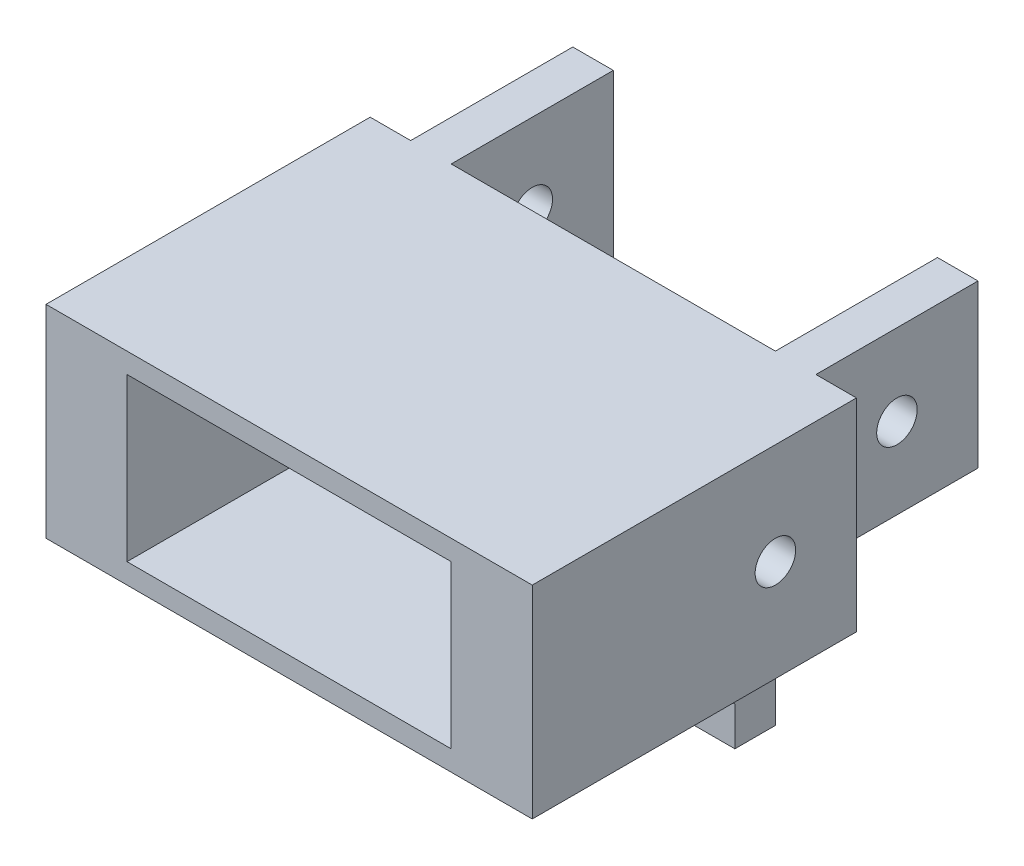
SolidWorks part; units mm, degrees
note: The reader was unsure of these and kept them because the rebuilt part matched: shared geometry of "Esquisse1<6>", "Esquisse1<8>", "Esquisse1<9>", "Esquisse37<5>".
ref_plane "Plan de face" through (0, 0, 0) normal (0, 0, 1) x (1, 0, 0)
ref_plane "Plan de dessus" through (0, 0, 0) normal (0, 1, 0) x (1, 0, 0)
ref_plane "Plan de droite" through (0, 0, 0) normal (1, 0, 0) x (0, 0, -1)
sketch "Esquisse1" plane through (0, 0, 0) normal (0, 0, 1) x (1, 0, 0)
  line L0 (-16.8286, 20.0498) -> (23.1714, 20.0498)
  line L1 (23.1714, 20.0498) -> (23.1714, 0.0498)
  line L2 (23.1714, 0.0498) -> (28.1714, 0.0498)
  line L3 (28.1714, 0.0498) -> (28.1714, 20.0498)
  line L4 (33.1714, 20.0498) -> (33.1714, -4.9502)
  line L5 (33.1714, -4.9502) -> (23.1714, -4.9502)
  line L6 (23.1714, -4.9502) -> (23.1714, -19.9502)
  line L7 (23.1714, -19.9502) -> (-16.8286, -19.9502)
  line L8 (-16.8286, -19.9502) -> (-16.8286, -4.9502)
  line L9 (-16.8286, -4.9502) -> (-26.8286, -4.9502)
  line L10 (-26.8286, -4.9502) -> (-26.8286, 20.0498)
  line L11 (28.1714, 20.0498) -> (33.1714, 20.0498)
  line L12 (-26.8286, 20.0498) -> (-21.8286, 20.0498)
  line L13 (-21.8286, 20.0498) -> (-21.8286, 0.0498)
  line L14 (-21.8286, 0.0498) -> (-16.8286, 0.0498)
  line L15 (-16.8286, 0.0498) -> (-16.8286, 20.0498)
  line L16 (-21.8286, 20.0498) -> (-16.8286, 20.0498)
  line L17 (23.1714, 20.0498) -> (28.1714, 20.0498)
  line L18 (23.1714, -4.9502) -> (-16.8286, -4.9502)
  circle A0 centre (-6.8286, -9.9502) radius 2.5
  circle A1 centre (13.1714, -9.9502) radius 2.5
  dimension "D19" = 5
  dimension "D20" = 5
  dimension "D21" = 10
  dimension "D22" = 5
  dimension "D23" = 5
  dimension "D24" = 10
  dimension "D1" = 20
  dimension "D2" = 40
  dimension "D3" = 5
  dimension "D4" = 20
  dimension "D5" = 5
  dimension "D6" = 25
  dimension "D7" = 10
  dimension "D8" = 15
  dimension "D9" = 40
  dimension "D10" = 15
  dimension "D11" = 10
  dimension "D12" = 25
  dimension "D13" = 5
  dimension "D14" = 20
  dimension "D15" = 5
  dimension "D16" = 20
  dimension "D17" = 5
  dimension "D18" = 5
extrude "Boss.-Extru.2" add sketch "Esquisse1" along normal blind 5 contours L18 L8 L7 L6
sketch "Esquisse10" plane through (0, 0, 5) normal (0, 0, 1) x (1, 0, 0)
  point P0 (13.1714, -9.9502)
hole_wizard "Diamètre du perçage Ø5.0 (5)1" positions "Esquisse10" profile "Esquisse9" hole size "Ø5.0" standard "BSI" end condition through all
sketch "Esquisse9" plane through (13.1714, -9.9502, 5) normal (1, 0, 0) x (0, -1, 0)
  line L0 (0, 0) -> (0, 5)
  line L1 (0, 5) -> (2.5, 5)
  line L2 (2.5, 5) -> (2.5, 0)
  line L5 (2.5, 0) -> (0, 0)
  line L11 (0, -6.35) -> (0, 107.95) construction
  dimension "Diamètre du perçage jusqu'au prochain" = 5
  dimension "Profondeur du perçage jusqu'au prochain" = 5
sketch "Esquisse13" plane through (0, 0, 5) normal (0, 0, 1) x (1, 0, 0)
  point P0 (-6.8286, -9.9502)
hole_wizard "Diamètre du perçage Ø5.0 (5)2" positions "Esquisse13" profile "Esquisse12" hole size "Ø5.0" standard "BSI" end condition through all
sketch "Esquisse12" plane through (-6.8286, -9.9502, 5) normal (1, 0, 0) x (0, -1, 0)
  line L0 (0, 0) -> (0, 5)
  line L1 (0, 5) -> (2.5, 5)
  line L2 (2.5, 5) -> (2.5, 0)
  line L5 (2.5, 0) -> (0, 0)
  line L11 (0, -6.35) -> (0, 107.95) construction
  dimension "Diamètre du perçage jusqu'au prochain" = 5
  dimension "Profondeur du perçage jusqu'au prochain" = 5
extrude "Boss.-Extru.3" add sketch "Esquisse1<6>" along normal blind 40 contours L9 L10 L12 L16 L0 L17 L11 L4 L5 L18
sketch "Esquisse1<6>" plane through (0, 0, 0) normal (0, 0, 1) x (1, 0, 0) same geometry as "Esquisse1"
extrude "Boss.-Extru.4" add sketch "Esquisse1<8>" against normal blind 20 contours L17 L3 L2 L1
sketch "Esquisse1<8>" plane through (0, 0, 0) normal (0, 0, 1) x (1, 0, 0) same geometry as "Esquisse1"
extrude "Boss.-Extru.5" add sketch "Esquisse1<9>" against normal blind 20 contours L15 L16 L13 L14
sketch "Esquisse1<9>" plane through (0, 0, 0) normal (0, 0, 1) x (1, 0, 0) same geometry as "Esquisse1"
ref_plane "Plan4" through (-21.8286, 20.0498, -20) normal (0, 0, 1) x (1, 0, 0)
sketch "Esquisse26" plane through (-21.8286, 0, 0) normal (-1, 0, 0) x (0, 0, 1)
  line L0 (-20, 20.0498) -> (0, 20.0498) construction
  line L1 (0, 20.0498) -> (0, -4.9502) construction
  circle A0 centre (-10, 10.0498) radius 2.5
  point P0 (-10, 10.0498)
  dimension "D1" = 10
  dimension "D2" = 10
  dimension "D3" = 5
sketch "Esquisse27" plane through (28.1714, 0, 0) normal (1, 0, 0) x (0, 0, -1)
  line L0 (20, 20.0498) -> (0, 20.0498) construction
  line L1 (0, -4.9502) -> (0, 20.0498) construction
  circle A0 centre (10, 10.0498) radius 2.5
  point P0 (10, 10.0498)
  dimension "D1" = 10
  dimension "D2" = 10
  dimension "D3" = 5
hole_wizard "Diamètre du perçage Ø5.0 (5)7" positions "Esquisse27" profile "Esquisse28" hole size "Ø5.0" standard "DIN"
sketch "Esquisse28" plane through (28.1714, 10.0498, -10) normal (0, 1, 0) x (0, 0, -1)
  line L0 (0, 0) -> (0, 5)
  line L1 (0, 5) -> (2.5, 5)
  line L2 (2.5, 5) -> (2.5, 0)
  line L5 (2.5, 0) -> (0, 0)
  line L11 (0, -6.35) -> (0, 107.95) construction
  dimension "Diamètre du perçage jusqu'au prochain" = 5
  dimension "Profondeur du perçage jusqu'au prochain" = 5
hole_wizard "Diamètre du perçage Ø5.0 (5)8" positions "Esquisse26" profile "Esquisse29" hole size "Ø5.0" standard "DIN" end condition up to next
sketch "Esquisse29" plane through (-21.8286, 10.0498, -10) normal (0, 1, 0) x (0, 0, 1)
  line L0 (0, 0) -> (0, 5)
  line L1 (0, 5) -> (2.5, 5)
  line L2 (2.5, 5) -> (2.5, 0)
  line L5 (2.5, 0) -> (0, 0)
  line L11 (0, -6.35) -> (0, 107.95) construction
  dimension "Diamètre du perçage jusqu'au prochain" = 5
  dimension "Profondeur du perçage jusqu'au prochain" = 5
sketch "Esquisse30" plane through (0, 0, 40) normal (0, 0, 1) x (1, 0, 0)
  line L1 (-16.8286, 17.5498) -> (23.1714, 17.5498)
  line L2 (-16.8286, 17.5498) -> (-16.8286, -2.4502)
  line L3 (-16.8286, -2.4502) -> (23.1714, -2.4502)
  line L4 (23.1714, 17.5498) -> (23.1714, -2.4502)
  line L7 (-16.8286, 20.0498) -> (23.1714, 20.0498) construction
  line L8 (33.1714, 20.0498) -> (33.1714, -4.9502) construction
  dimension "D1" = 40
  dimension "D2" = 20
  dimension "D3" = 2.5
  dimension "D4" = 10
extrude "Enlèv. mat.-Extru.1" cut sketch "Esquisse30" against normal blind 35 contours L1 L4 L3 L2
sketch "Esquisse35" plane through (33.1714, 0, 0) normal (1, 0, 0) x (0, 0, -1)
  line L0 (-40, 20.0498) -> (0, 20.0498) construction
  line L1 (0, -4.9502) -> (0, 20.0498) construction
  circle A0 centre (-10, 7.5498) radius 2.5
  point P0 (-10, 7.5498)
  dimension "D1" = 5
  dimension "D2" = 12.5
  dimension "D3" = 10
hole_wizard "Diamètre du perçage Ø5.0 (5)10" positions "Esquisse35" profile "Esquisse36" hole size "Ø5.0" standard "DIN" end condition through all
sketch "Esquisse36" plane through (33.1714, 7.5498, 10) normal (0, 1, 0) x (0, 0, -1)
  line L0 (0, 0) -> (0, 60)
  line L1 (0, 60) -> (2.5, 60)
  line L2 (2.5, 60) -> (2.5, 0)
  line L5 (2.5, 0) -> (0, 0)
  line L11 (0, -6.35) -> (0, 107.95) construction
  dimension "Diamètre du perçage jusqu'au prochain" = 5
  dimension "Profondeur du perçage jusqu'au prochain" = 60
sketch "Esquisse37" plane through (0, 0, 5) normal (0, 0, 1) x (1, 0, 0)
  line L0 (23.1714, -4.9502) -> (-16.8286, -4.9502) construction
  line L1 (-16.8286, -4.9502) -> (-13.8286, -4.9502)
  line L2 (-16.8286, -4.9502) -> (-16.8286, -14.9502)
  line L3 (-16.8286, -14.9502) -> (-13.8286, -14.9502)
  line L4 (-13.8286, -4.9502) -> (-13.8286, -14.9502)
  line L5 (20.1714, -4.9502) -> (23.1714, -4.9502)
  line L6 (20.1714, -4.9502) -> (20.1714, -15.1699)
  line L7 (20.1714, -15.1699) -> (23.1714, -15.1699)
  line L8 (23.1714, -4.9502) -> (23.1714, -15.1699)
  line L9 (23.1714, -4.9502) -> (23.1714, -19.9502) construction
  line L11 (1.81, -4.9502) -> (4.81, -4.9502)
  line L12 (1.81, -4.9502) -> (1.81, -14.9502)
  line L13 (1.81, -14.9502) -> (4.81, -14.9502)
  line L14 (4.81, -4.9502) -> (4.81, -14.9502)
  dimension "D1" = 3
  dimension "D2" = 10
  dimension "D3" = 3
  dimension "D4" = 10.2197
  dimension "D5" = 10
  dimension "D6" = 3
extrude "Boss.-Extru.6" add sketch "Esquisse37" along normal blind 10 contours L1 L4 L3 L2
sketch "Esquisse38" plane through (-16.8286, 0, 0) normal (-1, 0, 0) x (0, 0, 1)
  line L0 (15, -4.9502) -> (5, -14.9502)
extrude "Boss.-Extru.7" add sketch "Esquisse37<5>" along normal blind 10
sketch "Esquisse37<5>" plane through (0, 0, 5) normal (0, 0, 1) x (1, 0, 0) same geometry as "Esquisse37"
extrude "Enlèv. mat.-Extru.4" cut sketch "Esquisse38" against normal blind 3 and the other way through all contours L0
sketch "Esquisse40" plane through (1.81, 0, 0) normal (-1, 0, 0) x (0, 0, 1)
  line L0 (15, -4.9502) -> (5, -14.9502)
extrude "Enlèv. mat.-Extru.5" cut sketch "Esquisse40" against normal blind 3 and the other way through all
sketch "Esquisse41" plane through (20.1714, 0, 0) normal (-1, 0, 0) x (0, 0, 1)
  line L0 (15, -4.9502) -> (5, -15.1699)
extrude "Enlèv. mat.-Extru.6" cut sketch "Esquisse41" against normal blind 3 and the other way through all
